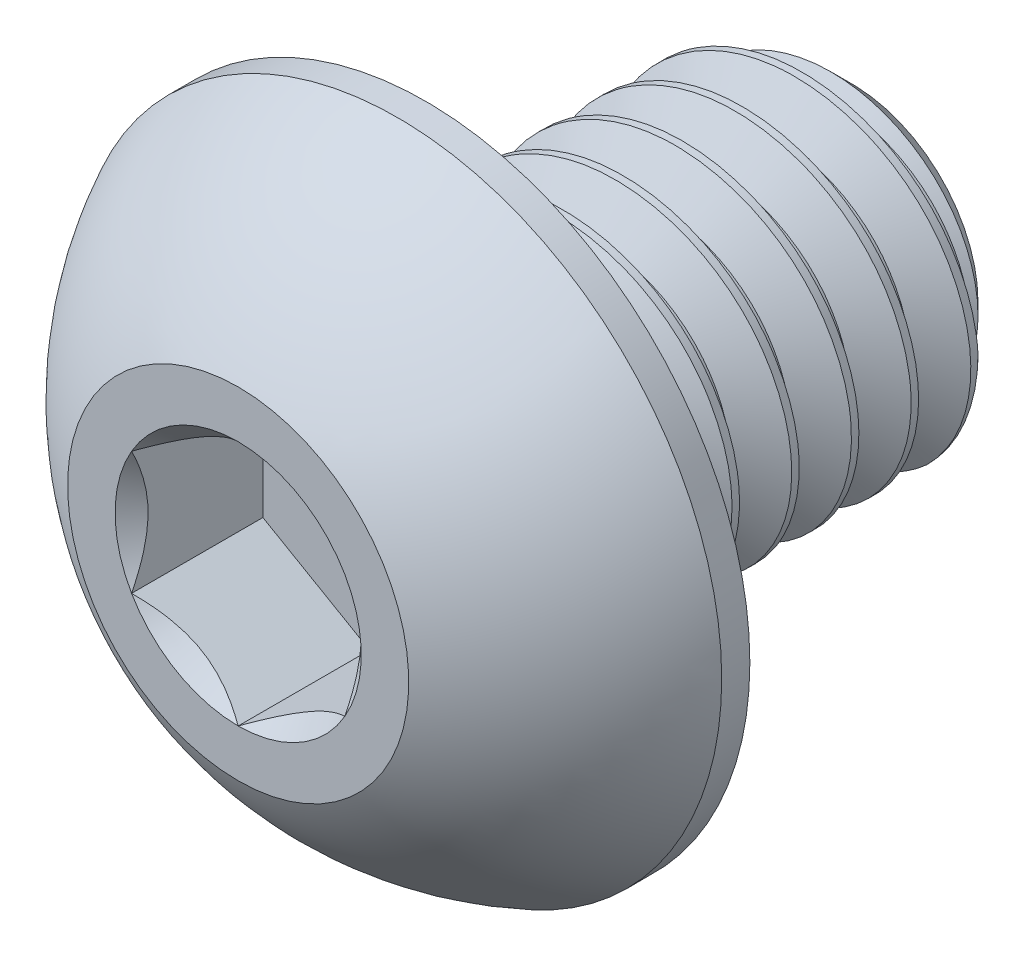
SolidWorks part; units mm, degrees
ref_plane "Front" through (0, 0, 0) normal (0, 0, 1) x (1, 0, 0)
ref_plane "Top" through (0, 0, 0) normal (0, 1, 0) x (1, 0, 0)
ref_plane "Right" through (0, 0, 0) normal (1, 0, 0) x (0, 0, -1)
sketch "Sketch1" plane through (0, 0, 0) normal (1, 0, 0) x (0, 0, -1)
  line L2 (2.2, 2) -> (7.2, 2)
  line L3 (7.2, 2) -> (7.2, 0)
  line L4 (7.2, 0) -> (2.2, 0)
  line L6 (1.87, 3.8) -> (2.2, 3.8) construction
  line L7 (7.2, 2) -> (7.2, -2) construction
  line L8 (0, 0) -> (2.2, 0) construction
  line L9 (2.2, 3.8) -> (2.2, -3.8) construction
  line L11 (2.2, 2) -> (2.2, 0)
  line L13 (0, 1.25) -> (0, -1.25) construction
  line L14 (0, 1.25) -> (0, 2) construction
  line L15 (7.1562, 2.0758) -> (7.5062, 1.4696) construction
  line L16 (7.5062, 1.4696) -> (7.8562, 2.0758) construction
  line L17 (7.8562, 2.0758) -> (7.1562, 2.0758) construction
  line L18 (7.2, 2) -> (7.8125, 2) construction
  line L19 (7.5062, 2.0758) -> (7.5062, 2) construction
  line L20 (7.5062, 2) -> (7.5062, 1.5453) construction
  line L21 (7.5062, 1.5453) -> (7.5062, 1.4696) construction
  line L22 (7.4625, 1.5453) -> (7.55, 1.5453)
  line L23 (7.1781, 2.0379) -> (7.8344, 2.0379)
  line L24 (7.55, 1.5453) -> (7.8344, 2.0379)
  line L25 (7.4625, 1.5453) -> (7.1781, 2.0379)
  line L26 (6.675, 2) -> (7.2, 1.475)
  arc A3 (0, 2) -> (1.87, 3.8) centre (3.7264, 0) cw construction
  point P29 (7.5062, 2.0379)
  point P30 (5.45, -2)
  dimension "D1" = 0.33
  dimension "Pitch" = 0.7
  dimension "D3" = 0.0875
  dimension "D2" = 0.525
  dimension "D4" = 45
  dimension "D5" = 1.75
sketch "Sketch10" plane through (0, 0, 0) normal (1, 0, 0) x (0, 0, -1)
  line L0 (6.675, 2) -> (7.2, 1.475) construction
  line L1 (6.675, 2) -> (7.2, 1.475)
  line L4 (7.2, 2) -> (2.2, 2)
  line L5 (7.2, 0) -> (7.2, 2)
  line L6 (2.2, 0) -> (7.2, 0)
  line L7 (2.2, 2) -> (2.2, 0)
  line L8 (6.675, 2) -> (2.2, 2)
  line L9 (7.2, 0) -> (7.2, 1.475)
  line L10 (2.2, 0) -> (7.2, 0)
  line L11 (2.2, 2) -> (2.2, 0)
  dimension "D1" = 0
revolve "Revolve3" add sketch "Sketch10" angle 360 about L8
sketch "Sketch7" plane through (0, 0, 0) normal (1, 0, 0) x (0, 0, -1)
  line L6 (1.87, 3.8) -> (2.2, 3.8) construction
  line L8 (0, 0) -> (2.2, 0) construction
  line L11 (2.2, 3.8) -> (2.2, -3.8) construction
  line L12 (1.87, 3.8) -> (2.2, 3.8)
  line L13 (0, 0) -> (2.2, 0)
  line L14 (0, 1.25) -> (0, -1.25) construction
  line L15 (2.2, 3.8) -> (2.2, 0)
  line L16 (0, 2) -> (0, 0)
  arc A2 (1.87, 3.8) -> (0, 2) centre (3.7264, 0) ccw construction
  arc A3 (1.87, 3.8) -> (0, 2) centre (3.7264, 0) ccw
revolve "Revolve2" add sketch "Sketch7" angle 360 mid plane about L13
sketch "Sketch5" plane through (0, 0, 0) normal (0, 0, 1) x (1, 0, 0)
  line L1 (1.25, -0.7217) -> (1.25, 0.7217)
  line L2 (1.25, 0.7217) -> (0, 1.4434)
  line L3 (0, 1.4434) -> (-1.25, 0.7217)
  line L4 (-1.25, 0.7217) -> (-1.25, -0.7217)
  line L5 (-1.25, -0.7217) -> (0, -1.4434)
  line L6 (0, -1.4434) -> (1.25, -0.7217)
  circle A0 centre (0, 0) radius 1.25 construction
extrude "Cut-Extrude2" cut sketch "Sketch5" against normal blind 1.54
sketch "Sketch6" plane through (0, 0, 0) normal (0, 0, 1) x (1, 0, 0)
  circle A0 centre (0, 0) radius 1.4434
extrude "Cut-Extrude3" cut sketch "Sketch6" against normal blind 1.54 draft 45
sketch "Sketch9" plane through (0, 0, -2.2) normal (0, 0, -1) x (-1, 0, 0)
  circle A0 centre (0, 0) radius 2 construction
  circle A4 centre (0, 0) radius 2
split "Split1" bodies to split 113 resulting bodies 123 124 split by face at (3.8, 0, -2.2)
sketch "Sketch11" plane through (0, 0, -7.2) normal (0, 0, -1) x (-1, 0, 0)
  circle A0 centre (0, 0) radius 2 construction
  circle A1 centre (0, 0) radius 2
curve "Helix/Spiral1" pitch 0.7 height 7.2 radius 2 centre (0, 0, -7.2) axis (0, 0, 1) start towards (0, 1, 0)
sketch "Sketch12" plane through (0, 0, 0) normal (1, 0, 0) x (0, 0, -1)
  line L0 (7.4625, 1.5453) -> (7.55, 1.5453) construction
  line L1 (7.55, 1.5453) -> (7.8344, 2.0379) construction
  line L2 (7.1781, 2.0379) -> (7.8344, 2.0379) construction
  line L3 (7.4625, 1.5453) -> (7.1781, 2.0379) construction
  line L4 (7.4625, 1.5453) -> (7.55, 1.5453)
  line L5 (7.55, 1.5453) -> (7.8344, 2.0379)
  line L6 (7.1781, 2.0379) -> (7.8344, 2.0379)
  line L7 (7.4625, 1.5453) -> (7.1781, 2.0379)
sweep "Cut-Sweep2" cut profiles "Sketch12" path "Helix/Spiral1" align with end faces yes
extrude "Boss-Extrude1" add sketch "Sketch9" along normal blind 10 draft 45
equation "\"D1@Cut-Extrude2\" = \"Head Ht@Sketch1\" * .7"
equation "\"D1@Sketch1\" = \"Head Ht@Sketch1\" * .15"
equation "\"D1@Cut-Extrude3\" = \"D1@Cut-Extrude2\""
equation "\"D3@Sketch1\" = \"Pitch@Sketch1\" / 8"
equation "\"D2@Sketch1\"=\"Pitch@Sketch1\"*0.75"
equation "\"D3@Helix/Spiral1\" = \"Lg@Sketch1\" + \"Head Ht@Sketch1\""
equation "\"D4@Helix/Spiral1\"=\"pitch@sketch1\""
equation "\"D5@Sketch1\"=\"Pitch@Sketch1\"*2.5"
